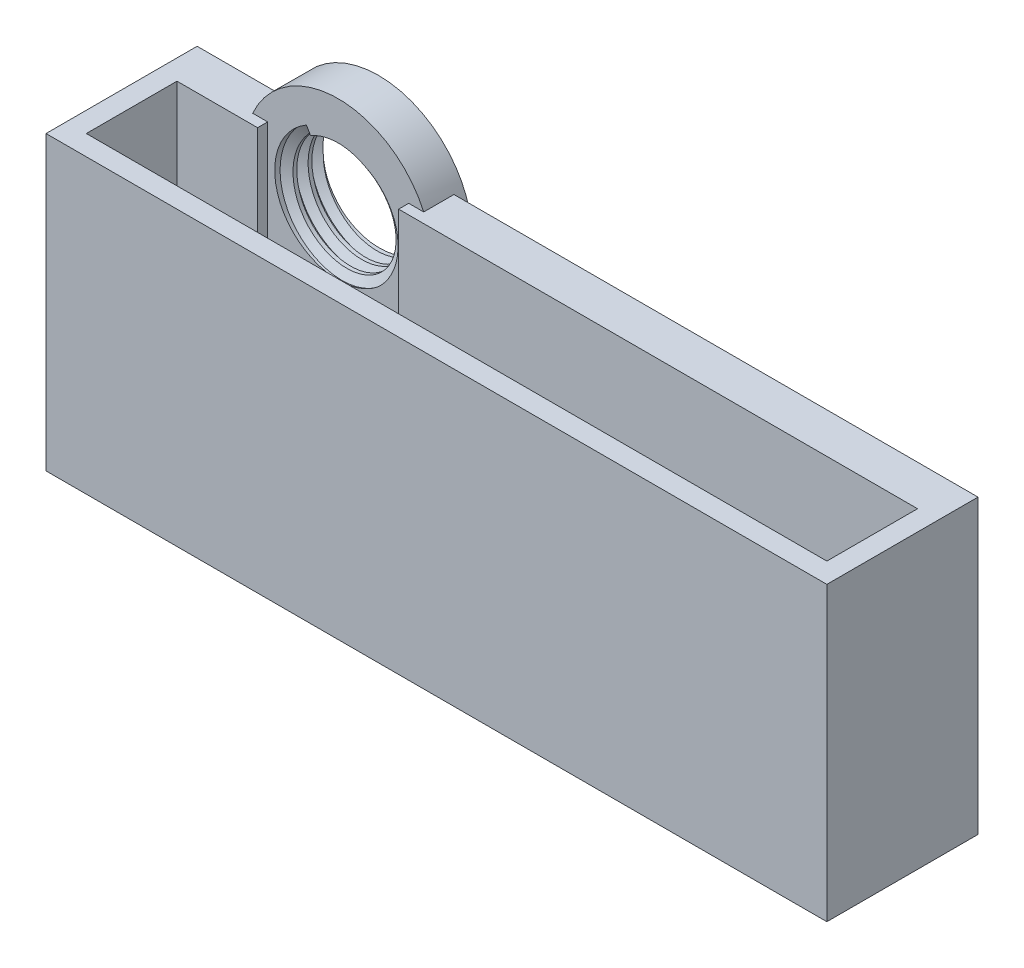
SolidWorks part; units mm, degrees
ref_plane "Ebene vorne" through (0, 0, 0) normal (0, 0, 1) x (1, 0, 0)
ref_plane "Ebene oben" through (0, 0, 0) normal (0, 1, 0) x (1, 0, 0)
ref_plane "Ebene rechts" through (0, 0, 0) normal (1, 0, 0) x (0, 0, -1)
sketch "Skizze1" plane through (0, 0, 0) normal (0, 0, 1) x (1, 0, 0)
  line L1 (38.75, -14.5) -> (-38.75, -14.5)
  line L2 (38.75, -14.5) -> (38.75, 14.5)
  line L3 (38.75, 14.5) -> (-38.75, 14.5)
  line L4 (-38.75, -14.5) -> (-38.75, 14.5)
  line L5 (38.75, -14.5) -> (-38.75, 14.5) construction
  line L6 (38.75, 14.5) -> (-38.75, -14.5) construction
  point P0 (0, 0)
  dimension "D1" = 77.5
  dimension "D2" = 29
extrude "Aufsatz-Linear austragen1" add sketch "Skizze1" along normal blind 15
ref_plane "Ebene für Handyschlitz" through (0, 14.5, 0) normal (0, 1, 0) x (1, 0, 0)
sketch "Skizze2" plane through (0, 14.5, 0) normal (0, 1, 0) x (1, 0, 0)
  line L5 (36.75, -13) -> (-36.75, -13)
  line L6 (36.75, -13) -> (36.75, -4)
  line L7 (36.75, -4) -> (-36.75, -4)
  line L8 (-36.75, -13) -> (-36.75, -4)
  line L9 (36.75, -13) -> (-36.75, -4) construction
  line L10 (36.75, -4) -> (-36.75, -13) construction
  point P6 (0, -8.5)
  dimension "D1" = 73.5
  dimension "D5" = 9
extrude "Schnitt-Linear austragen2" cut sketch "Skizze2" against normal blind 27
sketch "Skizze3" plane through (0, 14.5, 0) normal (0, 1, 0) x (1, 0, 0)
  line L6 (-36.75, -4) -> (-36.75, -13) construction
  line L8 (-28.75, -3) -> (-14.75, -3)
  line L9 (-28.75, -3) -> (-28.75, -6.7753)
  line L10 (-28.75, -6.7753) -> (-14.75, -6.7753)
  line L11 (-14.75, -3) -> (-14.75, -6.7753)
  dimension "D1" = 14
  dimension "D2" = 22
extrude "Schnitt-Linear austragen3" cut sketch "Skizze3" against normal blind 27
sketch "Skizze4" plane through (0, 0, 3) normal (0, 0, 1) x (1, 0, 0)
  line L0 (-38.75, 14.5) -> (-38.75, -14.5) construction
  line L5 (-38.75, -14.5) -> (38.75, -14.5) construction
  circle A0 centre (-21.75, 10.7) radius 9.3
  dimension "D3" = 18.6
  dimension "D1" = 17
  dimension "D2" = 25.2
extrude "Aufsatz-Linear austragen2" add sketch "Skizze4" against normal blind 4
sketch "Skizze5" plane through (0, 0, 0) normal (0, 0, -1) x (-1, 0, 0)
  circle A0 centre (21.75, 10.7) radius 6.3
extrude "Schnitt-Linear austragen4" cut sketch "Skizze5" along normal blind 4 and the other way blind 4
thread "Gewinde1" pitch 1.5 method extrude profile "Gewindeprofil1" start angle 0, offset 1.6, length 5, pitch 1.5, diameter 12.6
ref_plane "Ebene3" through (-15.45, 10.7, -2.6) normal (0, -1, 0) x (1, 0, 0)
sketch "Gewindeprofil1" plane through (-15.45, 10.7, -2.6) normal (0, -1, 0) x (1, 0, 0)
  line L0 (0, 0) -> (0, 1.5) construction
  line L11 (0, 0) -> (0, 1.3125)
  line L12 (0, 1.3125) -> (-0.8119, 0.8437)
  line L13 (-0.8119, 0.8437) -> (-0.8119, 0.4687)
  line L15 (-0.8119, 0.4687) -> (0, 0)
  line L17 (-0.8119, 0.6562) -> (0, 0.6562) construction
  point P2 (0, 0)
  dimension "Pitch" = 1.5
  dimension "Profile_Angle" = 60
  dimension "Profile_Land" = 0.375
  dimension "Profile_Height" = 0.8119
sketch "Skizze8" plane through (0, 0, 3) normal (0, 0, 1) x (1, 0, 0)
  circle A0 centre (-21.75, 10.7) radius 6.7628
extrude "Schnitt-Linear austragen5" cut sketch "Skizze8" along normal blind 3
sketch "Skizze9" plane through (0, 0, -1) normal (0, 0, -1) x (-1, 0, 0)
  circle A0 centre (21.75, 10.7) radius 8.0452
extrude "Schnitt-Linear austragen6" cut sketch "Skizze9" along normal blind 3
